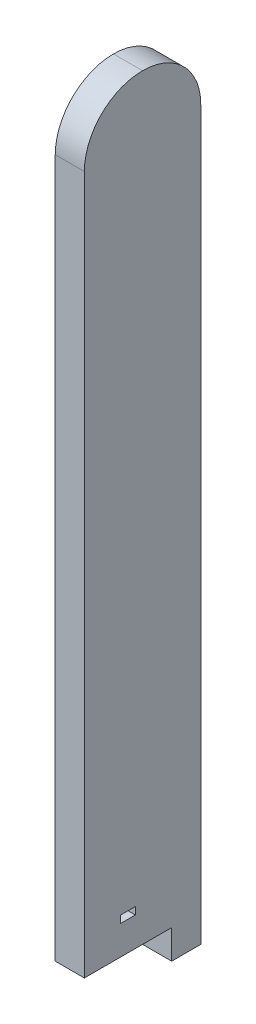
SolidWorks part; units mm, degrees
ref_plane "Front Plane" through (0, 0, 0) normal (0, 0, 1) x (1, 0, 0)
ref_plane "Top Plane" through (0, 0, 0) normal (0, 1, 0) x (1, 0, 0)
ref_plane "Right Plane" through (0, 0, 0) normal (1, 0, 0) x (0, 0, -1)
sketch "Sketch1" plane through (0, 0, 0) normal (1, 0, 0) x (0, 0, -1)
  line L0 (12.7, -69.5376) -> (12.7, -158.75)
  line L1 (-12.7, 12.7) -> (12.7, 12.7)
  line L2 (-12.7, 12.7) -> (-12.7, -152.4)
  line L3 (-12.7, -152.4) -> (6.35, -152.4)
  line L4 (12.7, 12.7) -> (12.7, -69.5376)
  line L5 (122.4964, -180.3089) -> (-252.9602, -112.2658) construction
  line L7 (12.7, -158.75) -> (6.35, -158.75)
  line L8 (6.35, -158.75) -> (6.35, -152.4)
  line L9 (4.503, -155.575) -> (-49995.497, -155.575) construction
  line L11 (-12.7, 12.7) -> (0, 0) construction
  line L12 (0, 0) -> (12.7, 12.7) construction
  circle A0 centre (0, 0) radius 155.575 construction
  point P0 (0, 0)
  point P11 (6.35, -155.575)
  dimension "D1" = 25.4
  dimension "D2" = 6.35
  dimension "D3" = 6.35
extrude "Boss-Extrude1" add sketch "Sketch1" along normal mid plane 6.35
fillet "Fillet1" radius 12.7 2 edges at (0, 12.7, -12.7) (0, 12.7, 12.7)
sketch "Sketch2" plane through (3.175, 0, 0) normal (1, 0, 0) x (0, 0, -1)
  line L1 (-4.7625, -146.05) -> (-1.5875, -146.05)
  line L2 (-4.7625, -146.05) -> (-4.7625, -144.4625)
  line L3 (-4.7625, -144.4625) -> (-1.5875, -144.4625)
  line L4 (-1.5875, -146.05) -> (-1.5875, -144.4625)
  line L5 (-4.7625, -146.05) -> (-1.5875, -144.4625) construction
  line L6 (-4.7625, -144.4625) -> (-1.5875, -146.05) construction
  line L7 (-3.175, -152.4) -> (-3.175, -145.2563) construction
  line L8 (-12.7, -152.4) -> (6.35, -152.4) construction
  point P0 (-3.175, -145.2563)
  dimension "D1" = 6.35
  dimension "D2" = 1.5875
  dimension "D3" = 3.175
extrude "Cable-tie hole" cut sketch "Sketch2" against normal through all
